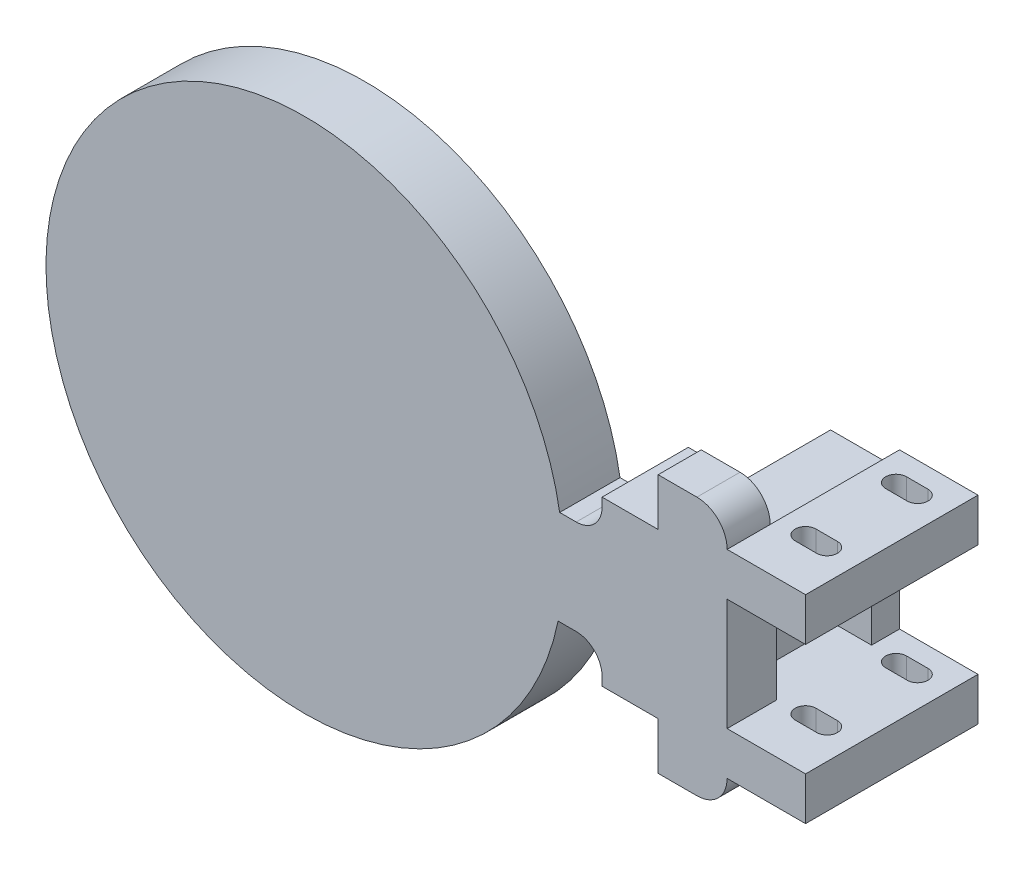
SolidWorks part; units mm, degrees
ref_plane "前基準面" through (0, 0, 0) normal (0, 0, 1) x (1, 0, 0)
ref_plane "上基準面" through (0, 0, 0) normal (0, 1, 0) x (1, 0, 0)
ref_plane "右基準面" through (0, 0, 0) normal (1, 0, 0) x (0, 0, -1)
ref_axis "基準軸1" through (0, -55, 0) along (0, 1, 0)
ref_axis "基準軸2" through (-88.99, 0, 0) along (1, 0, 0)
ref_axis "基準軸3" through (0, 0, 55) along (0, 0, -1)
sketch "草圖1" plane through (0, 0, 0) normal (1, 0, 0) x (0, 0, -1)
  line L1 (0, 0) -> (10, 0)
  line L2 (0, 0) -> (0, 19)
  line L3 (0, 19) -> (10, 19)
  line L4 (10, 0) -> (10, 19)
  dimension "D1" = 19
  dimension "D2" = 10
extrude "填料-伸長1" add sketch "草圖1" against normal blind 6.5
sketch "草圖2" plane through (0, 0, 0) normal (0, 0, 1) x (1, 0, 0)
  line L0 (0, -55) -> (0, 55) construction
  line L1 (3.575, 0) -> (-3.575, 0) construction
  line L2 (-11.4196, 15) -> (-6.5, 15)
  line L3 (-6.5, 19) -> (-6.5, 0) construction
  line L4 (-11.6061, 4) -> (-6.5, 4)
  line L5 (-88.99, 0) -> (88.99, 0) construction
  line L6 (-6.5, 19) -> (0, 19) construction
  line L7 (-6.5, 4) -> (-6.5, 15)
  arc A0 (-11.4196, 15) -> (-11.6061, 4) centre (-41, 10) ccw
  dimension "D1" = 60
  dimension "D2" = 41
  dimension "D3" = 10
  dimension "D4" = 4
  dimension "D5" = 4
extrude "填料-伸長2" add sketch "草圖2" against normal blind 7
fillet "圓角1" radius 3 1 edges at (-6.5, 9.5, -7)
sketch "草圖3" plane through (0, 0, 0) normal (1, 0, 0) x (0, 0, -1)
  line L1 (0, -5.5) -> (5, -5.5)
  line L2 (0, -5.5) -> (0, 24.5)
  line L3 (0, 24.5) -> (5, 24.5)
  line L4 (5, -5.5) -> (5, 24.5)
  line L5 (-55, 0) -> (55, 0) construction
  line L7 (0, -55) -> (0, 55) construction
  dimension "D1" = 30
  dimension "D2" = 5
  dimension "D3" = 24.5
extrude "填料-伸長3" add sketch "草圖3" along normal blind 8
sketch "草圖4" plane through (0, 0, -5) normal (0, 0, -1) x (-1, 0, 0)
  line L0 (-8, -5.5) -> (-8, 24.5) construction
  line L1 (0, 0) -> (-8, 0)
  line L2 (0, 0) -> (0, 19)
  line L3 (0, 19) -> (-8, 19)
  line L4 (-8, 0) -> (-8, 19)
  dimension "D1" = 19
extrude "填料-伸長4" add sketch "草圖4" along normal blind 15
ref_plane "平面1" through (0, 9.5, 0) normal (0, 1, 0) x (1, 0, 0)
sketch "草圖6" plane through (8, 0, 0) normal (1, 0, 0) x (0, 0, -1)
  line L0 (7.975, 9.5) -> (-7.975, 9.5) construction
  line L1 (5.75, 16) -> (16.75, 16)
  line L2 (5.75, 16) -> (5.75, 3)
  line L3 (5.75, 3) -> (16.75, 3)
  line L4 (16.75, 16) -> (16.75, 3)
  line L6 (5, 19) -> (5, 24.5) construction
  point P4 (5.75, 9.5)
  point P9 (11.25, 16)
  dimension "D1" = 11
  dimension "D2" = 13
  dimension "D3" = 6.25
extrude "除料-伸長1" cut sketch "草圖6" against normal blind 4
sketch "草圖8" plane through (0, 19, 0) normal (0, 1, 0) x (1, 0, 0)
  line L0 (13.6, 16.5) -> (11.1, 16.5) construction
  line L1 (8, 20) -> (17.1, 20)
  line L2 (8, 20) -> (8, 0)
  line L3 (8, 0) -> (17.1, 0)
  line L4 (17.1, 20) -> (17.1, 0)
  line L5 (13.6, 15.3) -> (11.1, 15.3)
  line L6 (13.6, 17.7) -> (11.1, 17.7)
  line L7 (13.6, 6) -> (11.1, 6) construction
  line L8 (13.6, 4.8) -> (11.1, 4.8)
  line L9 (13.6, 7.2) -> (11.1, 7.2)
  arc A2 (13.6, 15.3) -> (13.6, 17.7) centre (13.6, 16.5) ccw
  arc A3 (11.1, 17.7) -> (11.1, 15.3) centre (11.1, 16.5) ccw
  arc A4 (13.6, 4.8) -> (13.6, 7.2) centre (13.6, 6) ccw
  arc A5 (11.1, 7.2) -> (11.1, 4.8) centre (11.1, 6) ccw
  point P6 (12.35, 6)
  point P9 (12.35, 16.5)
  dimension "D3" = 1.2
  dimension "D9" = 1.2
  dimension "D11" = 2.5
  dimension "D1" = 9.1
  dimension "D2" = 20
  dimension "D4" = 3.5
  dimension "D5" = 14
  dimension "D7" = 5.6
  dimension "D8" = 5.6
  dimension "D10" = 2.5
extrude "填料-伸長5" add sketch "草圖8" against normal blind 3
mirror "鏡射1" about plane through (0, 9.5, 0) normal (0, 1, 0) of "填料-伸長5"
extrude "填料-伸長6" add sketch "草圖8<2>" along normal blind 2
sketch "草圖8<2>" plane through (0, 19, 0) normal (0, 1, 0) x (1, 0, 0) same geometry as "草圖8"
mirror "鏡射2" about plane through (0, 9.5, 0) normal (0, 1, 0) of "填料-伸長6"
fillet "圓角2" radius 3.5 2 edges at (8, 24.5, -2.5) (8, -5.5, -2.5)
fillet "圓角3" radius 3 2 edges at (-6.5, 4, -5) (-6.5, 15, -5)
